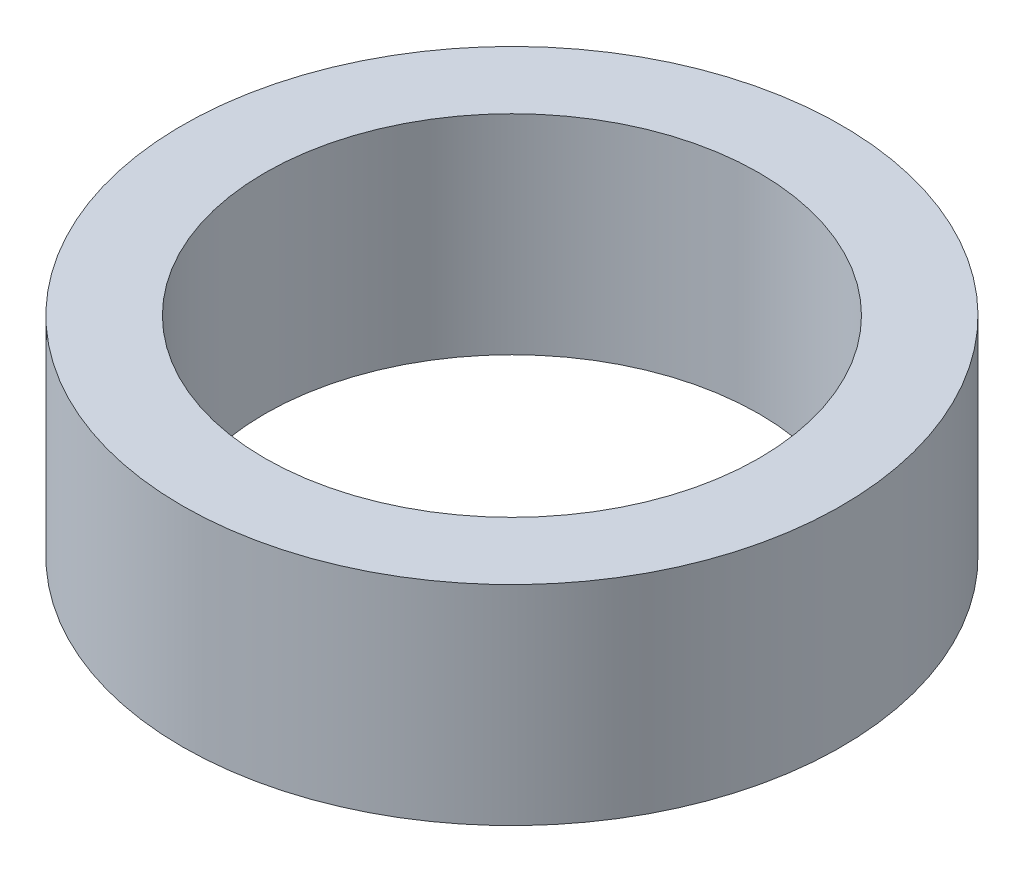
SolidWorks part; units mm, degrees
ref_plane "Front Plane" through (0, 0, 0) normal (0, 0, 1) x (1, 0, 0)
ref_plane "Top Plane" through (0, 0, 0) normal (0, 1, 0) x (1, 0, 0)
ref_plane "Right Plane" through (0, 0, 0) normal (1, 0, 0) x (0, 0, -1)
sketch "Sketch1" plane through (0, 0, 0) normal (0, 1, 0) x (1, 0, 0)
  circle A0 centre (0, 0) radius 30
  dimension "FLANGE_OD" = 60
extrude "Boss-Extrude1" add sketch "Sketch1" along normal blind 19
sketch "Sketch2" plane through (0, 0, 0) normal (0, 1, 0) x (1, 0, 0)
  circle A0 centre (0, 0) radius 22.5
  dimension "BORE_D" = 45
extrude "Cut-Extrude1" cut sketch "Sketch2" along normal through all
sketch "Sketch3" plane through (0, 19, 0) normal (0, 1, 0) x (1, 0, 0)
  circle A0 centre (0, 0) radius 12.8795 construction
  circle A1 centre (-12.8795, 0) radius 1.5
  dimension "BOLT_D" = 3
  dimension "BOLT_PCD" = 25.7591
extrude "Cut-Extrude2" cut sketch "Sketch3" against normal blind 14.9836 rebuild error yes
pattern_circular "CirPattern1" count 4 over 360 rebuild error yes
